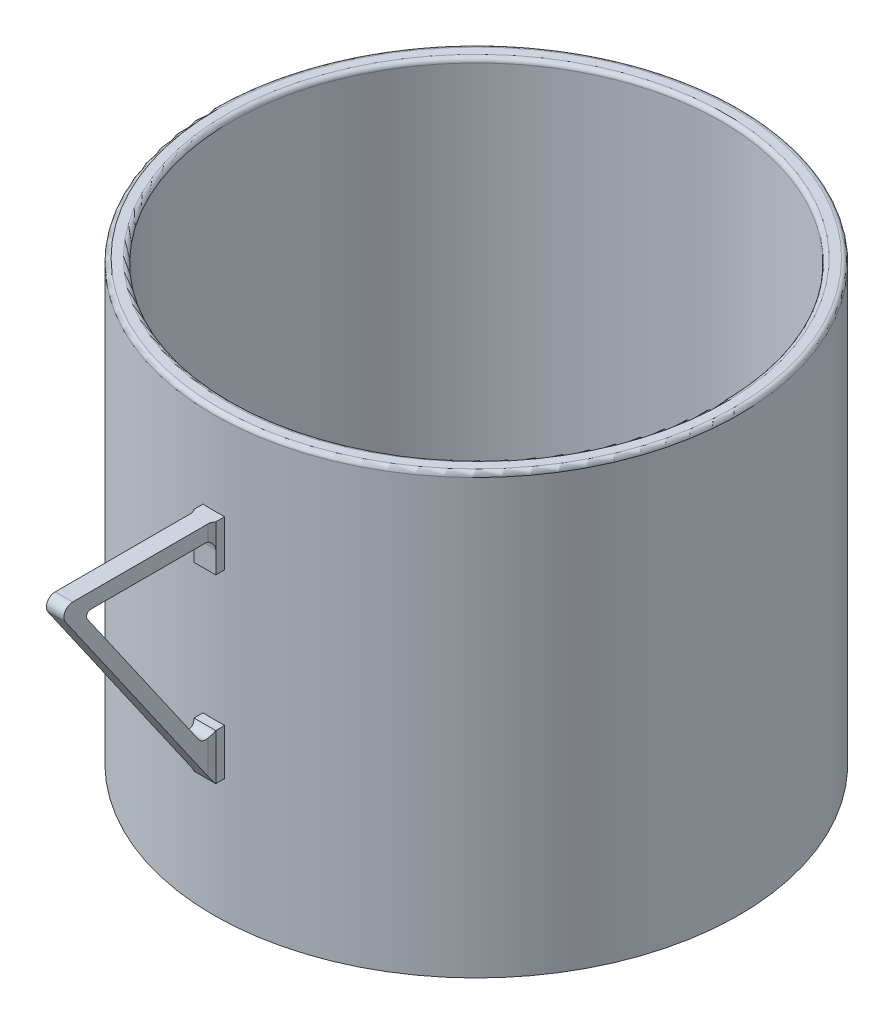
SolidWorks part; units mm, degrees
ref_plane "정면" through (0, 0, 0) normal (0, 0, 1) x (1, 0, 0)
ref_plane "윗면" through (0, 0, 0) normal (0, 1, 0) x (1, 0, 0)
ref_plane "우측면" through (0, 0, 0) normal (1, 0, 0) x (0, 0, -1)
sketch "스케치1" plane through (0, 0, 0) normal (0, 1, 0) x (1, 0, 0)
  circle A0 centre (0, 0) radius 60
extrude "보스-돌출1" add sketch "스케치1" along normal blind 100 contours A0
shell "쉘1" thickness 4 removed face at (0, 100, 60)
ref_plane "평면2" through (0, 0, 60) normal (0, 0, 1) x (1, 0, 0)
sketch "스케치3" plane through (0, 0, 60) normal (0, 0, 1) x (1, 0, 0)
  line L1 (-2.4806, 69.5528) -> (2.4806, 69.5528)
  line L2 (-2.4806, 69.5528) -> (-2.4806, 80.0587)
  line L3 (-2.4806, 80.0587) -> (2.4806, 80.0587)
  line L4 (2.4806, 69.5528) -> (2.4806, 80.0587)
  line L5 (-2.4806, 69.5528) -> (2.4806, 80.0587) construction
  line L6 (-2.4806, 80.0587) -> (2.4806, 69.5528) construction
  line L7 (-2.4806, 28.2585) -> (2.4806, 28.2585)
  line L8 (-2.4806, 28.2585) -> (-2.4806, 38.7645)
  line L9 (-2.4806, 38.7645) -> (2.4806, 38.7645)
  line L10 (2.4806, 28.2585) -> (2.4806, 38.7645)
  line L11 (-2.4806, 28.2585) -> (2.4806, 38.7645) construction
  line L12 (-2.4806, 38.7645) -> (2.4806, 28.2585) construction
  point P0 (0, 74.8057)
  point P5 (0, 33.5115)
extrude "보스-돌출2" add sketch "스케치3" along normal blind 2 and the other way up to surface contours L4 L3 L2 L1 other way up to face at (0, 100, 60)
extrude "보스-돌출3" add sketch "스케치3<3>" along normal blind 2 and the other way up to surface contours L9 L10 L7 L8 other way up to face at (0, 0, 60)
sketch "스케치3<3>" plane through (0, 0, 60) normal (0, 0, 1) x (1, 0, 0) same geometry as "스케치3"
ref_plane "평면3" through (0, 0, 0) normal (1, 0, 0) x (0, 0, -1)
sketch "스케치4" plane through (0, 0, 0) normal (1, 0, 0) x (0, 0, -1)
  line L0 (-62, 80.0587) -> (-98.0387, 80.0587)
  line L1 (-98.0387, 80.0587) -> (-62, 28.2585)
  line L2 (-62, 28.2585) -> (-62, 33.5115)
  line L3 (-62, 28.2585) -> (-62, 38.7645) construction
  line L4 (-62, 33.5115) -> (-91.949, 76.5587)
  line L5 (-91.949, 76.5587) -> (-62, 76.5587)
  line L6 (-62, 69.5528) -> (-62, 80.0587) construction
  line L7 (-62, 76.5587) -> (-62, 80.0587)
  line L8 (-62, 69.5528) -> (-62, 80.0587) construction
  dimension "D1" = 3.5
  dimension "D2" = 3
extrude "보스-돌출4" add sketch "스케치4" along normal mid plane 4 contours L0 L1 L2 L4 L5 L7
fillet "필렛2" radius 2 1 edges at (0, 80.0587, 98.0387)
fillet "필렛3" radius 2 1 edges at (-2, 78.3087, 62)
fillet "필렛4" radius 2 5 edges at (-0.2403, 76.5587, 62) (0, 33.5115, 62) (2, 30.885, 62) (-2, 30.885, 62) (2, 78.3087, 62)
fillet "필렛5" radius 1 1 edges at (0, 100, 60)
fillet "필렛6" radius 1 1 edges at (0, 100, 56)
fillet "필렛7" radius 1 1 edges at (0, 76.5587, 91.949)
